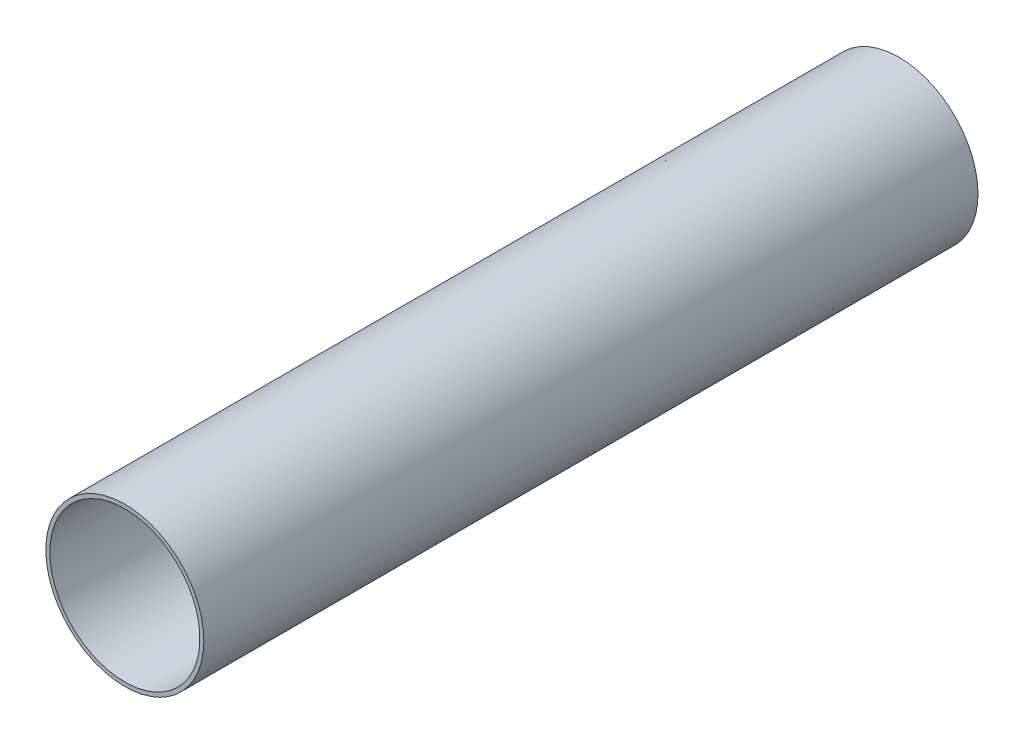
SolidWorks part; units mm, degrees
ref_plane "Front Plane" through (0, 0, 0) normal (0, 0, 1) x (1, 0, 0)
ref_plane "Top Plane" through (0, 0, 0) normal (0, 1, 0) x (1, 0, 0)
ref_plane "Right Plane" through (0, 0, 0) normal (1, 0, 0) x (0, 0, -1)
sketch "Sketch1" plane through (0, 0, 0) normal (0, 0, 1) x (1, 0, 0)
  circle A0 centre (0, 0) radius 50
  dimension "D1" = 100
extrude "Boss-Extrude1" add sketch "Sketch1" against normal blind 245 and the other way blind 245
sketch "Sketch2" plane through (0, 0, -245) normal (0, 0, -1) x (-1, 0, 0)
  circle A0 centre (0, 0) radius 47.5
  dimension "D1" = 95
extrude "Cut-Extrude25" cut sketch "Sketch2" against normal through all both and the other way through all
